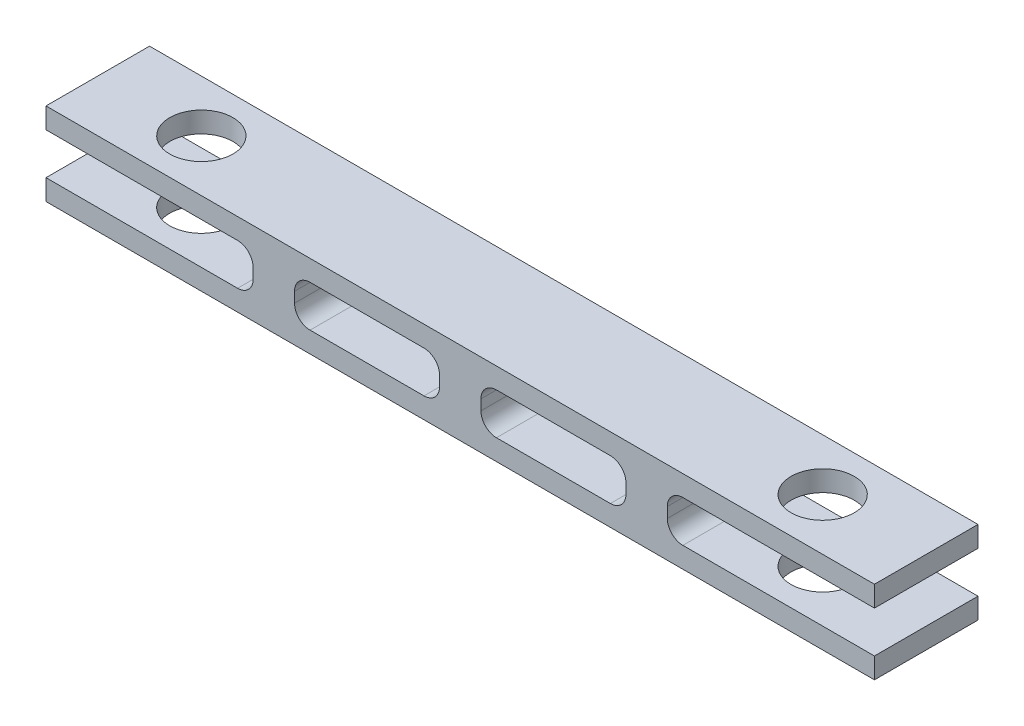
SolidWorks part; units mm, degrees
ref_plane "Front Plane" through (0, 0, 0) normal (0, 0, 1) x (1, 0, 0)
ref_plane "Top Plane" through (0, 0, 0) normal (0, 1, 0) x (1, 0, 0)
ref_plane "Right Plane" through (0, 0, 0) normal (1, 0, 0) x (0, 0, -1)
sketch "Sketch1" plane through (0, 0, 0) normal (0, 1, 0) x (1, 0, 0)
  line L1 (0, 0) -> (40, 0)
  line L2 (0, 0) -> (0, 5)
  line L3 (0, 5) -> (40, 5)
  line L4 (40, 0) -> (40, 5)
  dimension "D1" = 40
  dimension "D2" = 5
extrude "Boss-Extrude1" add sketch "Sketch1" along normal blind 4
sketch "Sketch2" plane through (0, 4, 0) normal (0, 1, 0) x (1, 0, 0)
  line L0 (0, 5) -> (0, 0) construction
  line L7 (20, 5) -> (20, 0) construction
  line L8 (40, 5) -> (0, 5) construction
  line L9 (0, 0) -> (40, 0) construction
  circle A0 centre (5, 2.5) radius 1.525
  circle A1 centre (35, 2.5) radius 1.525
  point P4 (0, 2.5)
  dimension "D1" = 3.05
  dimension "D2" = 5
extrude "Cut-Extrude1" cut sketch "Sketch2" against normal through all
sketch "Sketch3" plane through (0, 0, -5) normal (0, 0, -1) x (-1, 0, 0)
  line L0 (-40, 4) -> (-40, 0) construction
  line L1 (-40, 3) -> (-30, 3)
  line L2 (-40, 3) -> (-40, 1)
  line L3 (-40, 1) -> (-30, 1)
  line L4 (-30, 3) -> (-30, 1)
  line L5 (-20, 4) -> (-20, 0) construction
  line L6 (-28, 3) -> (-21, 3)
  line L7 (-28, 3) -> (-28, 1)
  line L8 (-28, 1) -> (-21, 1)
  line L9 (-21, 3) -> (-21, 1)
  line L14 (-40, 4) -> (0, 4) construction
  line L15 (-40, 0) -> (0, 0) construction
  line L16 (-19, 3) -> (-19, 1)
  line L17 (-12, 1) -> (-19, 1)
  line L18 (-12, 3) -> (-12, 1)
  line L19 (-12, 3) -> (-19, 3)
  line L20 (-10, 3) -> (-10, 1)
  line L21 (0, 1) -> (-10, 1)
  line L22 (0, 3) -> (0, 1)
  line L23 (0, 3) -> (-10, 3)
  point P10 (-40, 2)
  point P11 (-40, 2)
  point P12 (-28, 2)
  point P13 (-30, 2)
  dimension "D1" = 10
  dimension "D2" = 2
  dimension "D3" = 2
  dimension "D4" = 7
extrude "Cut-Extrude2" cut sketch "Sketch3" against normal through all
fillet "Fillet1" radius 0.75 12 edges at (12, 1, -2.5) (21, 1, -2.5) (30, 1, -2.5) (30, 3, -2.5) (10, 1, -2.5) (19, 1, -2.5) (28, 1, -2.5) (12, 3, -2.5) (21, 3, -2.5) (10, 3, -2.5) (19, 3, -2.5) (28, 3, -2.5)
equation "\"columnWidth\"= 2"
equation "\"gapWidth\"= \"riserWidth\" / 2 - \"gapFromEdge\" - ( \"columnWidth\" * \"columnNumber\" )"
equation "\"columnNumber\"= 1.5"
equation "\"gapFromEdge\"= 10"
equation "\"riserWidth\"= 40"
equation "\"D1@Sketch1\"=\"riserWidth\""
equation "\"D1@Sketch3\"=\"gapFromEdge\""
equation "\"D3@Sketch3\"=\"columnWidth\""
equation "\"D4@Sketch3\"=\"gapWidth\""
